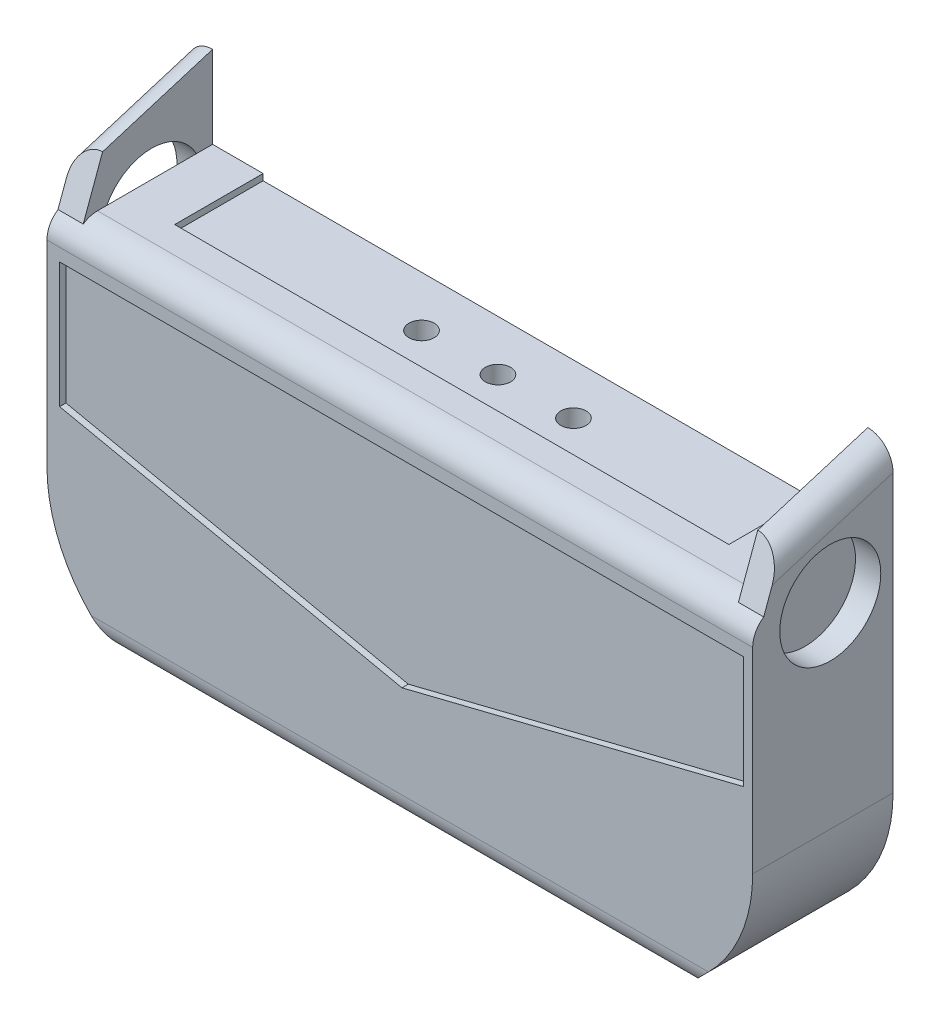
SolidWorks part; units mm, degrees
ref_plane "Front Plane" through (0, 0, 0) normal (0, 0, 1) x (1, 0, 0)
ref_plane "Top Plane" through (0, 0, 0) normal (0, 1, 0) x (1, 0, 0)
ref_plane "Right Plane" through (0, 0, 0) normal (1, 0, 0) x (0, 0, -1)
ref_plane "Plane1" through (0, 0, 67.9882) normal (0, 0, -1) x (-1, 0, 0)
sketch "Sketch4" plane through (0, 0, 67.9882) normal (0, 0, -1) x (-1, 0, 0)
  line L0 (28.4011, 35.8721) -> (28.4011, 98.6978)
  line L1 (28.4011, 98.6978) -> (-83.3366, 98.6978)
  line L2 (-83.3366, 98.6978) -> (-83.3366, 35.8721)
  line L3 (-83.3366, 35.8721) -> (28.4011, 35.8721)
extrude "Boss-Extrude3" add sketch "Sketch4" against normal blind 20.2263
sketch "Sketch5" plane through (0, 0, 88.2145) normal (0, 0, 1) x (1, 0, 0)
  line L0 (79.3366, 98.6978) -> (-24.4011, 98.6978)
  line L1 (-24.4011, 98.6978) -> (-24.4011, 91.8726)
  line L2 (-24.4011, 91.8726) -> (79.3366, 91.8726)
  line L3 (79.3366, 91.8726) -> (79.3366, 98.6978)
extrude "Cut-Extrude1" cut sketch "Sketch5" against normal through all
sketch "Sketch6" plane through (0, 0, 88.2145) normal (0, 0, 1) x (1, 0, 0)
  line L0 (-21.4011, 66.2058) -> (-21.4011, 42.8721)
  line L1 (-21.4011, 42.8721) -> (76.3366, 42.8721)
  line L2 (76.3366, 42.8721) -> (76.3366, 66.0985)
  line L3 (76.3366, 81.6562) -> (76.3366, 84.8726)
  line L4 (76.3366, 84.8726) -> (-21.4011, 84.8726)
  line L5 (-21.4011, 84.8726) -> (-21.4011, 81.5489)
  arc A0 (-21.4011, 81.5489) -> (-21.4011, 66.2058) centre (-17.4144, 73.8774) cw
  arc A1 (76.3366, 66.0985) -> (76.3366, 81.6562) centre (72.5731, 73.8774) cw
extrude "Cut-Extrude2" cut sketch "Sketch6" against normal through all
sketch "Sketch7" plane through (0, 91.8726, 0) normal (0, 1, 0) x (-1, 0, 0)
  line L0 (16.4011, 67.9882) -> (16.4011, 81.9882)
  line L1 (16.4011, 81.9882) -> (-71.3366, 81.9882)
  line L2 (-71.3366, 81.9882) -> (-71.3366, 67.9882)
  line L3 (-71.3366, 67.9882) -> (16.4011, 67.9882)
extrude "Cut-Extrude3" cut sketch "Sketch7" against normal blind 1
sketch "Sketch8" plane through (0, 35.8721, 0) normal (0, -1, 0) x (1, 0, 0)
  line L0 (71.3366, 67.9882) -> (71.3366, 81.9882)
  line L1 (71.3366, 81.9882) -> (-16.4011, 81.9882)
  line L2 (-16.4011, 81.9882) -> (-16.4011, 67.9882)
  line L3 (-16.4011, 67.9882) -> (71.3366, 67.9882)
extrude "Cut-Extrude4" cut sketch "Sketch8" against normal blind 1
draft "Draft1" type of draft neutral plane draft angle 17.058 faces to draft 2 face at (-26.4011, 98.6978, 78.1014) face at (81.3366, 98.6978, 78.1014) neutral plane through (0, 0, 88.2145) neutral plane normal (0, 0, 1) parameters "D1"=17.058
hole_wizard "Ø16.0 (16) Diameter Hole1" positions "Sketch10" profile "Sketch9" hole size "Ø16.0" standard "ANSI Metric"
sketch "Sketch10" plane through (-28.4011, 0, 0) normal (-1, 0, 0) x (0, 0, 1)
  point P0 (77.6441, 88.1585)
sketch "Sketch9" plane through (-28.4011, 88.1585, 77.6441) normal (0, 1, 0) x (0, 0, 1)
  line L0 (0, 0) -> (0, 4)
  line L1 (0, 4) -> (8, 4)
  line L2 (8, 4) -> (8, 0)
  line L5 (8, 0) -> (0, 0)
  line L10 (0, 4) -> (-8, 4) construction
  line L11 (0, -6.35) -> (0, 107.95) construction
  dimension "Hole Dia." = 16
  dimension "Hole Depth" = 4
  dimension "Drill Angle" = 180
hole_wizard "Ø16.0 (16) Diameter Hole2" positions "Sketch12" profile "Sketch11" hole size "Ø16.0" standard "ANSI Metric"
sketch "Sketch12" plane through (83.3366, 0, 0) normal (1, 0, 0) x (0, 0, -1)
  point P0 (-77.9303, 87.8661)
sketch "Sketch11" plane through (83.3366, 87.8661, 77.9303) normal (0, 1, 0) x (0, 0, -1)
  line L0 (0, 0) -> (0, 4)
  line L1 (0, 4) -> (8, 4)
  line L2 (8, 4) -> (8, 0)
  line L5 (8, 0) -> (0, 0)
  line L10 (0, 4) -> (-8, 4) construction
  line L11 (0, -6.35) -> (0, 107.95) construction
  dimension "Hole Dia." = 16
  dimension "Hole Depth" = 4
  dimension "Drill Angle" = 180
hole_wizard "Ø4.0 (4) Diameter Hole1" positions "Sketch14" profile "Sketch13" hole size "Ø4.0" standard "ANSI Metric"
sketch "Sketch14" plane through (0, 90.8726, 0) normal (0, 1, 0) x (1, 0, 0)
  point P0 (40.7133, -75.9695)
  point P1 (28.7614, -75.9695)
  point P2 (16.6624, -75.9695)
sketch "Sketch13" plane through (40.7133, 90.8726, 75.9695) normal (1, 0, 0) x (0, 0, 1)
  line L0 (0, 0) -> (0, 6)
  line L1 (0, 6) -> (2, 6)
  line L2 (2, 6) -> (2, 0)
  line L5 (2, 0) -> (0, 0)
  line L11 (0, -6.35) -> (0, 107.95) construction
  dimension "Thru Hole Dia." = 4
  dimension "Thru Hole Depth" = 6
hole_wizard "Ø4.0 (4) Diameter Hole2" positions "Sketch16" profile "Sketch15" hole size "Ø4.0" standard "ANSI Metric"
sketch "Sketch16" plane through (0, 36.8721, 0) normal (0, -1, 0) x (-1, 0, 0)
  point P0 (-40.7133, -75.9695)
  point P1 (-28.7614, -75.9695)
  point P2 (-16.6624, -75.9695)
sketch "Sketch15" plane through (40.7133, 36.8721, 75.9695) normal (1, 0, 0) x (0, 0, -1)
  line L0 (0, 0) -> (0, 68.032)
  line L1 (0, 68.032) -> (2, 68.032)
  line L2 (2, 68.032) -> (2, 0)
  line L5 (2, 0) -> (0, 0)
  line L11 (0, -6.35) -> (0, 107.95) construction
  dimension "Thru Hole Dia." = 4
  dimension "Thru Hole Depth" = 68.032
hole_wizard "M10 Clearance Hole1" positions "Sketch18" profile "Sketch17" hole size "M10" standard "ANSI Metric"
sketch "Sketch18" plane through (0, 0, 67.9882) normal (0, 0, -1) x (-1, 0, 0)
  point P0 (-72.5731, 73.8774)
  point P1 (17.4144, 73.8774)
sketch "Sketch17" plane through (72.5731, 73.8774, 67.9882) normal (1, 0, 0) x (0, 1, 0)
  line L0 (0, 0) -> (0, 20.2263)
  line L1 (0, 20.2263) -> (5.95, 20.2263)
  line L2 (5.95, 20.2263) -> (5.95, 0)
  line L5 (5.95, 0) -> (0, 0)
  line L11 (0, -6.35) -> (0, 107.95) construction
  dimension "Thru Hole Dia." = 11.9
  dimension "Thru Hole Depth" = 20.2263
chamfer "Chamfer1" distance 6.8251 angle 20.045 1 edges at (81.3366, 98.6978, 88.2145) first distance on face at (66.6231, 73.8774, 88.2145)
chamfer "Chamfer2" distance 6.8251 angle 20.045 1 edges at (-26.4011, 98.6978, 88.2145) first distance on face at (66.6231, 73.8774, 88.2145)
sketch "Sketch19" plane through (0, 0, 88.2145) normal (0, 0, 1) x (1, 0, 0)
  line L0 (-28.4011, 91.8726) -> (-28.4011, 35.8721)
  line L1 (-28.4011, 35.8721) -> (83.3366, 35.8721)
  line L2 (83.3366, 35.8721) -> (83.3366, 91.8726)
  line L3 (83.3366, 91.8726) -> (-28.4011, 91.8726)
extrude "Boss-Extrude4" add sketch "Sketch19" along normal blind 2 contours L3 L0 L1 L2
fillet "Fillet7" radius 4 1 edges at (27.4678, 91.8726, 90.2145)
chamfer "Chamfer3" distance 11 angle 45 1 edges at (83.3366, 35.8721, 79.1014)
chamfer "Chamfer4" distance 11 angle 45 1 edges at (-28.4011, 35.8721, 79.1014)
fillet "Fillet9" radius 24 1 edges at (83.3366, 46.8721, 79.1014)
fillet "Fillet10" radius 24 1 edges at (-28.4011, 46.8721, 79.1014)
sketch "Sketch21" plane through (0, 0, 90.2145) normal (0, 0, 1) x (1, 0, 0)
  line L0 (-26.3915, 85.8655) -> (-26.3915, 66.0226)
  line L1 (-26.3915, 66.0226) -> (27.8079, 54.5705)
  line L2 (27.8079, 54.5705) -> (81.8939, 68.0636)
  line L3 (81.8939, 68.0636) -> (81.8939, 85.8655)
  line L4 (81.8939, 85.8655) -> (-26.3915, 85.8655)
extrude "Cut-Extrude6" cut sketch "Sketch21" against normal blind 1
fillet "Fillet13" radius 4 1 edges at (-28.4011, 102.2311, 76.6993)
fillet "Fillet14" radius 4 1 edges at (83.3366, 102.2311, 76.6993)
fillet "Fillet15" radius 4 1 edges at (27.4678, 35.8721, 90.2145)
